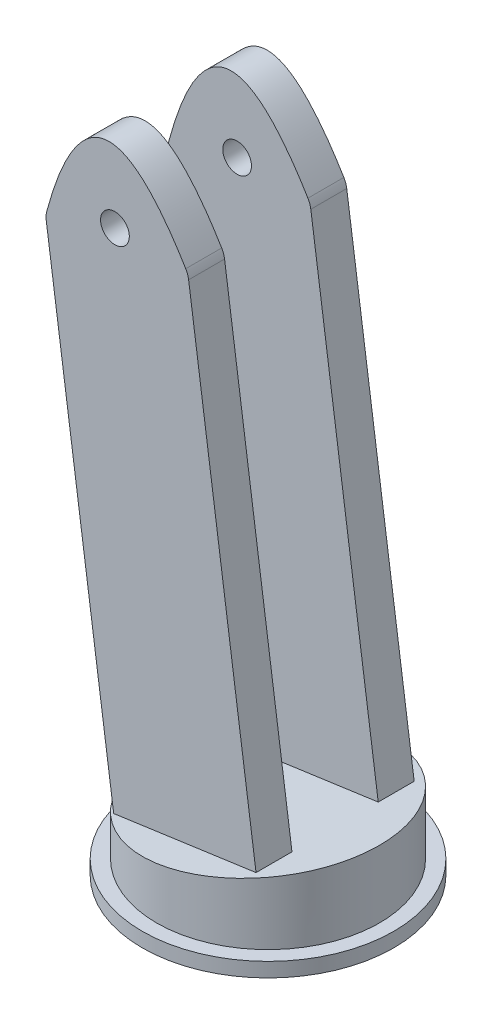
SolidWorks part; units mm, degrees
note: '?' marks a value the reader was unsure of.
ref_plane "Alzado" through (0, 0, 0) normal (0, 0, 1) x (1, 0, 0)
ref_plane "Planta" through (0, 0, 0) normal (0, 1, 0) x (1, 0, 0)
ref_plane "Vista lateral" through (0, 0, 0) normal (1, 0, 0) x (0, 0, -1)
sketch "Croquis2" plane through (0, 0, 0) normal (0, 1, 0) x (1, 0, 0)
  circle A0 centre (0, 0) radius 17.5
  dimension "D1" = 35
extrude "Saliente-Extruir1" add sketch "Croquis2" along normal blind 2
ref_plane "Plano1" through (0, 7, 0) normal (0, 1, 0) x (1, 0, 0)
ref_plane "Plano2" through (-15.5, 0, 0) normal (1, 0, 0) x (0, 0, -1)
ref_axis "Eje1" through (-15.5, 7, -19.25) along (0, 0, 1)?
ref_plane "Plano3" through (-1.265, 9.0006, 0) normal (-0.1392, 0.9903, 0) x (0, 0, 1)
sketch "Croquis3" plane through (0, 2, 0) normal (0, 1, 0) x (1, 0, 0)
  circle A0 centre (0, 0) radius 15.5
  dimension "D1" = 31
extrude "Saliente-Extruir2" add sketch "Croquis3" along normal blind 10
other "Cortar con superficie2" flip cut yes
sketch "Croquis6" plane through (-1.265, 9.0006, 0) normal (-0.1392, 0.9903, 0) x (0.9903, 0.1392, 0)
  line L1 (-9.3, -11) -> (10.7, -11)
  line L2 (-9.3, -11) -> (-9.3, -6)
  line L3 (-9.3, -6) -> (10.7, -6)
  line L4 (10.7, -11) -> (10.7, -6)
  point P4 (0.7, -6)
  dimension "D1" = 6
  dimension "D2" = 5
  dimension "D3" = 20
  dimension "D4" = 10.7
extrude "Saliente-Extruir4" add sketch "Croquis6" along normal blind 80
sketch "Croquis7" plane through (0, 0, 11) normal (0, 0, 1) x (1, 0, 0)
  line L0 (-21.6083, 86.9277) -> (-10.4744, 7.7063) construction
  line L1 (-21.6083, 86.9277) -> (-1.8029, 89.7112) construction
  line L2 (-1.8029, 89.7112) -> (9.3309, 10.4898) construction
  line L3 (19.704, 11.9476) -> (-22.2339, 6.0536) construction
  circle A1 centre (-10.3002, 78.3195) radius 2
  spline S0 degree 2 poles (-19.9382, 75.0445) (-13.3757, 100.2027) (-0.1329, 77.828) knots 0 0 0 1 1 1
  line M4 (9.3309, 10.4898) -> (-1.8029, 89.7112)
  line M5 (-1.8029, 89.7112) -> (-21.6083, 86.9277)
  line M6 (-21.6083, 86.9277) -> (-10.4744, 7.7063)
  dimension "D3" = 10
  dimension "D1" = 68
  dimension "D2" = 68
  dimension "D4" = 10
extrude "Cortar-Extruir4" cut sketch "Croquis7" against normal through all contours S0 M6 M5 | S0 M5 M4 | A1
mirror "Simetría1" about plane through (0, 0, 0) normal (0, 0, 1) of "Saliente-Extruir4", "Cortar-Extruir4"
fillet "Redondeo1" radius 3 4 edges at (-0.1329, 77.828, 8.5) (-19.9382, 75.0445, 8.5) (-0.1329, 77.828, -8.5) (-19.9382, 75.0445, -8.5)
ref_plane "Plano4" through (255.8411, 96.8953, -416) normal (0, -1, 0) x (-1, 0, 0)
